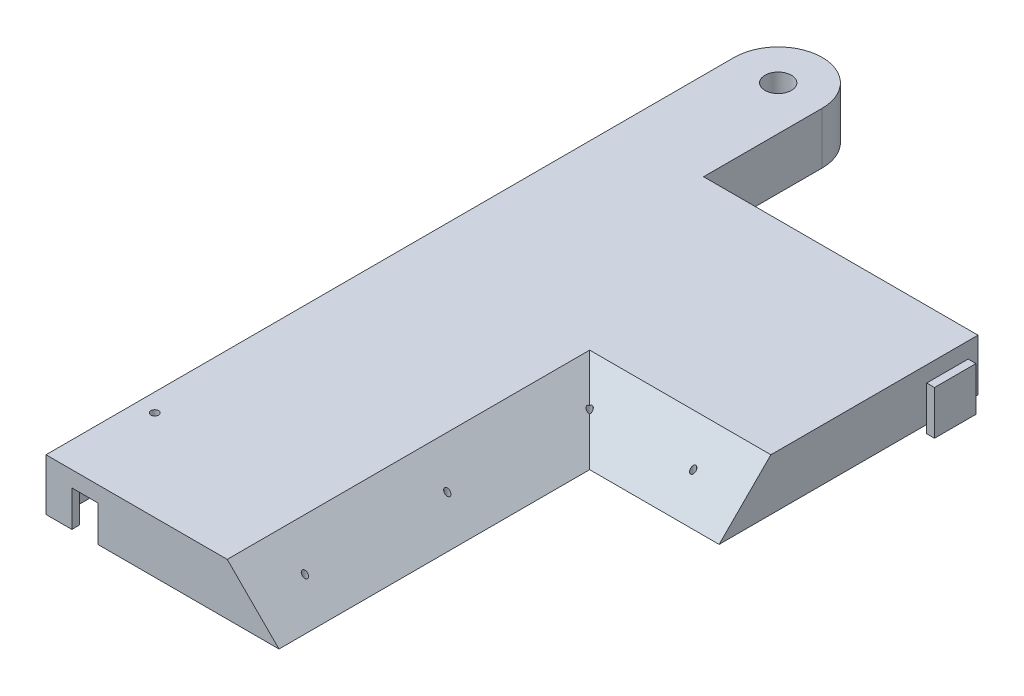
SolidWorks part; units mm, degrees
ref_plane "Front Plane" through (0, 0, 0) normal (0, 0, 1) x (1, 0, 0)
ref_plane "Top Plane" through (0, 0, 0) normal (0, 1, 0) x (1, 0, 0)
ref_plane "Right Plane" through (0, 0, 0) normal (1, 0, 0) x (0, 0, -1)
sketch "CornerrSketch1" plane through (0, 0, 0) normal (0, 1, 0) x (1, 0, 0)
  line L0 (140, 220) -> (140, 120)
  line L2 (0, 0) -> (0, 265.825)
  line L5 (140, 120) -> (90, 120)
  line L6 (90, 120) -> (90, 0)
  line L7 (0, 0) -> (90, 0)
  line L9 (34, 265.825) -> (34, 220)
  line L10 (34, 220) -> (140, 220)
  arc A0 (34, 265.825) -> (0, 265.825) centre (17, 265.825) ccw
  point P2 (17, 282.825)
  point P8 (0, 132.9125)
  dimension "D3" = 34
  dimension "D4" = 100
  dimension "D1" = 220
  dimension "D5" = 45.825
  dimension "D6" = 282.825
  dimension "D7" = 140
  dimension "D11" = 90
extrude "CornerBoss-Extrude1" add sketch "CornerrSketch1" along normal blind 20
shell "Shell2" thickness 3 removed face at (66, 0, -153.5813)
sketch "PutBackShellSketch2" plane through (0, 17, 0) normal (0, -1, 0) x (1, 0, 0)
  line L0 (67, -3) -> (87, -3)
  line L1 (87, -3) -> (87, -123)
  line L2 (87, -123) -> (137, -123)
  line L3 (137, -123) -> (137, -143)
  line L4 (137, -143) -> (67, -143)
  line L5 (67, -143) -> (67, -3)
  line L6 (87, -3) -> (87, -123) construction
  line L8 (87, -123) -> (137, -123) construction
  line L10 (137, -123) -> (137, -217) construction
  line L11 (90, -120) -> (140, -120) construction
  line L12 (3, -3) -> (87, -3) construction
  dimension "D1" = 23
extrude "PutBackShellBoss-Extrude1" add sketch "PutBackShellSketch2" along normal blind 17
sketch "Tab holes-Sketch1" plane through (0, 20, 0) normal (0, 1, 0) x (1, 0, 0)
  line L4 (140, 120) -> (140, 220) construction
  line L5 (90, 120) -> (140, 120) construction
  line L6 (0, 0) -> (90, 0) construction
  line L7 (90, 0) -> (90, 120) construction
  circle A0 centre (120, 130) radius 1
  circle A1 centre (80, 130) radius 1
  circle A2 centre (80, 75) radius 1
  circle A3 centre (80, 20) radius 1
  dimension "D5" = 2
  dimension "D7" = 55
  dimension "D3" = 55
  dimension "D6" = 20
  dimension "D1" = 10
  dimension "D4" = 20
  dimension "D2" = 10
extrude "TabHolesCut-Extrude1" cut sketch "Tab holes-Sketch1" against normal through all
sketch "PadSketch3" plane through (0, 17, 0) normal (0, -1, 0) x (1, 0, 0)
  line L0 (0, -265.825) -> (0, 0) construction
  line L1 (140, -220) -> (34, -220) construction
  circle A0 centre (17, -265.825) radius 12
  circle A1 centre (7, -35) radius 5
  dimension "D1" = 24
  dimension "D2" = 10
  dimension "D3" = 7
  dimension "D4" = 185
extrude "PadBoss-Extrude2" add sketch "PadSketch3" along normal blind 10
sketch "StepperShaftHoleSketch4" plane through (0, 7, 0) normal (0, -1, 0) x (1, 0, 0)
  circle A0 centre (17, -265.825) radius 5.1
  circle A1 centre (7, -35) radius 1.5
  dimension "D2" = 3
  dimension "D1" = 10.2
extrude "StepperShaftCut-Extrude2" cut sketch "StepperShaftHoleSketch4" against normal through all
sketch "ThreadedNutMountHolesSketch5" plane through (0, 7, 0) normal (0, -1, 0) x (-1, 0, 0)
  circle A8 centre (-17, 273.825) radius 1
  circle A9 centre (-9, 265.825) radius 1
  circle A10 centre (-17, 257.825) radius 1
  circle A11 centre (-25, 265.825) radius 1
  dimension "D1" = 2
  dimension "D2" = 8
  dimension "D3" = 16
  dimension "D4" = 8
  dimension "D5" = 16
extrude "ThreadedNutMountHolesCut-Extrude4" cut sketch "ThreadedNutMountHolesSketch5" against normal blind 10
sketch "TRPegSketch1" plane through (140, 0, 0) normal (1, 0, 0) x (0, 0, -1)
  line L0 (220, 20) -> (220, 0) construction
  line L1 (200.1, 13.9) -> (209.9, 13.9)
  line L2 (200.1, 13.9) -> (200.1, 0)
  line L3 (200.1, 0) -> (209.9, 0)
  line L4 (209.9, 13.9) -> (209.9, 0)
  line L5 (120, 0) -> (220, 0) construction
  point P6 (220, 10)
  dimension "D1" = 10.1
  dimension "D2" = 13.9
  dimension "D3" = 9.8
extrude "TRPegBoss-Extrude1" add sketch "TRPegSketch1" along normal blind 3.1
sketch "TRPegCapSketch2" plane through (143.1, 0, 0) normal (1, 0, 0) x (0, 0, -1)
  line L0 (200.1, 0) -> (209.9, 0) construction
  line L1 (197.1, 17) -> (213.1, 17)
  line L2 (197.1, 17) -> (197.1, 0)
  line L3 (197.1, 0) -> (213.1, 0)
  line L4 (213.1, 17) -> (213.1, 0)
  line L5 (200.1, 13.9) -> (200.1, 0) construction
  dimension "D1" = 16
  dimension "D2" = 3
  dimension "D3" = 17
extrude "TRPegCapBoss-Extrude2" add sketch "TRPegCapSketch2" along normal blind 3
sketch "BottomPegHoleSketch3" plane through (0, 0, 0) normal (0, 0, 1) x (1, 0, 0)
  line L0 (0, 0) -> (90, 0) construction
  line L1 (10, 13.9) -> (20, 13.9)
  line L2 (10, 13.9) -> (10, 0)
  line L3 (10, 0) -> (20, 0)
  line L4 (20, 13.9) -> (20, 0)
  line L5 (0, 20) -> (0, 0) construction
  line L6 (143.1, 13.9) -> (140, 13.9) construction
  dimension "D2" = 10
  dimension "D3" = 10
extrude "BottomPegHoleCut-Extrude1" cut sketch "BottomPegHoleSketch3" against normal blind 3
chamfer "OverlapChamfer1" distance 20 distance2 20 2 edges at (90, 20, -60) (115, 20, -120)
equation "\"RailThickness\"= .125in'Spec"
equation "\"StepperMountingHoleDistance\"= 31mm'Spec"
equation "\"StepperMountingHoleOffsetFromLeftOrRightSide\"= \"StepperMountingHoleOffsetFromItsSide\" + \"RailThickness\""
equation "\"StepperMountingHoleOffsetFromItsSide\"= 5.5mm'Spec"
equation "\"FrontBackRailLength\"= 510mm"
equation "\"DistanceBetweenLeftToRightStepperHoles\"= \"FrontBackRailLength\" - \"StepperMountingHoleOffsetFromLeftOrRightSide\" * 2 - \"StepperMountingHoleDistance\"'Equals 461.65"
equation "\"BedThickness\"= 20mm"
equation "\"BedToBuildPlateStandoffHoleSize\"= 3mm"
equation "\"BedLLongSide\"= \"BedThirdSize\" * 3'Equals 210"
equation "\"BedLShortSide\"= \"BedThirdSize\" * 2'Equals 140"
equation "\"BedLWidth\"= \"BedThirdSize\" + \"BedOverlap\"'Equals 90"
equation "\"D4@CornerrSketch1\"=\"BedLWidth\" + \"BedIncreasedByWidth\"/2"
equation "\"D1@CornerrSketch1\" = \"BedLLongSide\" + \"BedIncreasedByWidth\" / 2"
equation "\"BedInnerSquareWidth\"= \"BedThirdSize\" * 3'Equals 210"
equation "\"BedOverlap\"= 20mm"
equation "\"BedWidth\"= \"BedInnerSquareWidth\" + \"BedLWidth\" * 2 - \"BedOverlap\" * 2 + \"BedIncreasedByWidth\"'Equals 370"
equation "\"BedIncreasedByWidth\"= 20mm"
equation "\"BedIncreasedByLength\"= 0mm"
equation "\"BedThirdSize\"= 70mm"
equation "\"D3@Tab holes-Sketch1\"=55mm"
equation "\"D1@TRPegCapSketch2\"=\"BedTopPegCapWidth\""
equation "\"StandardWallThickness\"= 3mm"
equation "\"D2@TRPegCapSketch2\" = \"StandardWallThickness\""
equation "\"D3@TRPegCapSketch2\"=\"BedTopPegCapHeight\""
equation "\"D1@TRPegCapBoss-Extrude2\" = \"StandardWallThickness\""
equation "\"D1@BottomPegHoleCut-Extrude1\"=\"StandardWallThickness\""
equation "\"D1@Shell2\"=\"StandardWallThickness\""
equation "\"D2@TRPegSketch1\"=\"BedTopPegHeight\""
equation "\"D5@CornerrSketch1\"=\"DistanceFromBedSideToStepperHole\""
equation "\"DistanceFromBedFrontToStepperHole\"= \"LeadScrewNutPadSize\" + 10mm"
equation "\"DistanceFromBedSideToStepperHole\"= ( \"DistanceBetweenLeftToRightStepperHoles\" - \"BedWidth\" ) / 2'Equals 45.825"
equation "\"D7@CornerrSketch1\"= \"BedLShortSide\" + \"BedIncreasedByLength\" / 2"
equation "\"D3@CornerrSketch1\"=\"DistanceFromBedFrontToStepperHole\""
equation "\"BedToBuildPlateStandoffPadSize\"= 10mm"
equation "\"LeadScrewNutPadSize\"= \"LeadScrewNutMountingHoleFlangeDiameter\" + 2mm'Equals 24"
equation "\"D1@PadSketch3\" = \"LeadScrewNutPadSize\""
equation "\"D1@StepperShaftHoleSketch4\"=\"LeadScrewNutInnerShaftFlangeDiameter\""
equation "\"D11@CornerrSketch1\"=\"BedLWidth\""
equation "\"LeadScrewNutInnerShaftFlangeDiameter\"= 10.2mm'Spec"
equation "\"LeadScrewNutMountHoleDiameter\"= 2mm'Spec is 4.1 but smaller for tapping"
equation "\"LeadScrewNutMountingHoleFlangeDiameter\"= 22mm'Spec"
equation "\"LeadScrewNutMountingHoleDistance\"= 16mm'Spec"
equation "\"D2@ThreadedNutMountHolesSketch5\"=\"LeadScrewNutMountingHoleDistance\" / 2"
equation "\"D3@ThreadedNutMountHolesSketch5\"=\"LeadScrewNutMountingHoleDistance\""
equation "\"D5@ThreadedNutMountHolesSketch5\"=\"LeadScrewNutMountingHoleDistance\""
equation "\"D4@ThreadedNutMountHolesSketch5\"=\"LeadScrewNutMountingHoleDistance\"/2"
equation "\"D1@ThreadedNutMountHolesSketch5\"=\"LeadScrewNutMountHoleDiameter\""
equation "\"LeadScrewNutPadDepth\"= \"BedThickness\" / 2'Equals 10"
equation "\"D1@ThreadedNutMountHolesCut-Extrude4\"=\"LeadScrewNutPadDepth\""
equation "\"D2@PadSketch3\"=\"BedToBuildPlateStandoffPadSize\""
equation "\"D3@PadSketch3\"=\"BedToBuildPlateStandoffHolesDistanceFromFront\""
equation "\"BuildPlateWidth\"= 350mm'Spec"
equation "\"D4@PadSketch3\"=\"BedIncreasedByWidth\"/2 + \"BuildPlateWidth\"/2"
equation "\"D2@StepperShaftHoleSketch4\"=\"BedToBuildPlateStandoffHoleSize\""
equation "\"BuildPlateStandoffHolesDistanceFromFront\"= 7mm"
equation "\"BedToBuildPlateStandoffHolesDistanceFromFront\"= \"BuildPlateStandoffHolesDistanceFromFront\" + \"BedIncreasedByLength\" / 2'Equals 7"
equation "\"BedTopPegHoleWidth\"= 10mm"
equation "\"BedTopPegHoleHeight\"= \"BedThickness\"- \"StandardWallThickness\"* 2' Equals 14"
equation "\"BedTopPegWidth\"= \"BedTopPegHoleWidth\"- .1mm* 2'For easier assembly"
equation "\"BedTopPegHeight\"= \"BedTopPegHoleHeight\"- .1mm'For easier assembly"
equation "\"BedTopPegOffsetFromSide\"= 10mm"
equation "\"BedTopPegBoss\"= \"StandardWallThickness\"+ .1mm'For easier assembly"
equation "\"BedTopPegCapHeight\"= \"BedThickness\"- \"StandardWallThickness\"'Equals 17"
equation "\"BedTopPegCapWidth\"= \"BedThickness\"/2 + \"StandardWallThickness\"*2'Equals 16"
equation "\"D1@TRPegSketch1\"=\"BedTopPegOffsetFromSide\" + .1mm"
equation "\"D3@TRPegSketch1\"= \"BedTopPegWidth\""
equation "\"D1@TRPegBoss-Extrude1\"=\"BedTopPegBoss\""
equation "\"D3@BottomPegHoleSketch3\"=\"BedTopPegOffsetFromSide\""
equation "\"D2@BottomPegHoleSketch3\"=\"BedTopPegHoleWidth\""
equation "\"D6@Tab holes-Sketch1\"=\"BedOverlap\""
equation "\"D1@Tab holes-Sketch1\"=\"BedOverlap\"/2"
equation "\"D4@Tab holes-Sketch1\"=\"BedOverlap\""
equation "\"D2@Tab holes-Sketch1\"=\"BedOverlap\"/2"
equation "\"D1@PutBackShellSketch2\"=\"BedOverlap\" + \"StandardWallThickness\""
equation "\"D1@PutBackShellBoss-Extrude1\"=\"BedThickness\"- \"StandardWallThickness\""
equation "\"D1@OverlapChamfer1\"=\"BedThickness\""
equation "\"D3@OverlapChamfer1\"=\"BedOverlap\""
